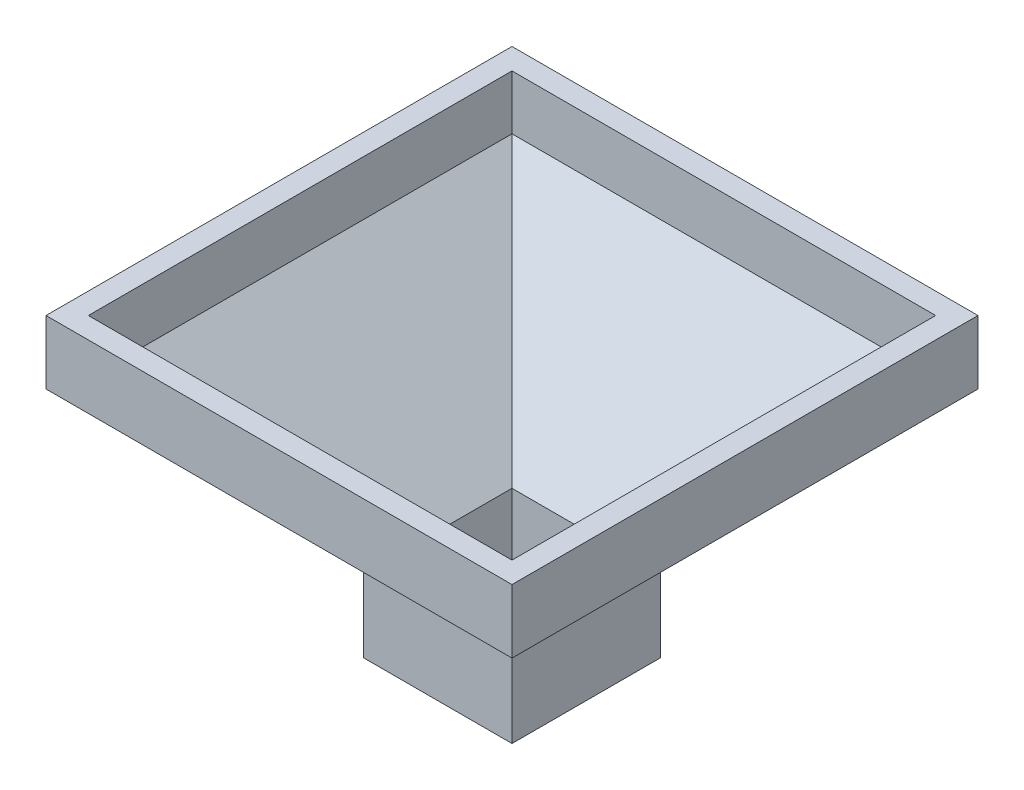
SolidWorks part; units mm, degrees
ref_plane "Alzado" through (0, 0, 0) normal (0, 0, 1) x (1, 0, 0)
ref_plane "Planta" through (0, 0, 0) normal (0, 1, 0) x (1, 0, 0)
ref_plane "Vista lateral" through (0, 0, 0) normal (1, 0, 0) x (0, 0, -1)
sketch "Croquis1" plane through (0, 0, 0) normal (0, 1, 0) x (1, 0, 0)
  line L1 (-110, -110) -> (110, -110)
  line L2 (-110, -110) -> (-110, 110)
  line L3 (-110, 110) -> (110, 110)
  line L4 (110, -110) -> (110, 110)
  line L5 (-110, -110) -> (110, 110) construction
  line L6 (-110, 110) -> (110, -110) construction
  point P0 (0, 0)
  dimension "D1" = 220
  dimension "D2" = 220
extrude "Saliente-Extruir1" add sketch "Croquis1" against normal blind 100
sketch "Croquis2" plane through (0, -100, 0) normal (0, -1, 0) x (1, 0, 0)
  line L1 (-35, -35) -> (35, -35)
  line L2 (-35, -35) -> (-35, 35)
  line L3 (-35, 35) -> (35, 35)
  line L4 (35, -35) -> (35, 35)
  line L5 (-35, -35) -> (35, 35) construction
  line L6 (-35, 35) -> (35, -35) construction
  point P0 (0, 0)
  dimension "D1" = 70
  dimension "D2" = 70
extrude "Cortar-Extruir1" cut sketch "Croquis2" against normal blind 70 draft 47 flip side to cut
sketch "Croquis3" plane through (0, -100, 0) normal (0, -1, 0) x (1, 0, 0)
  line L1 (-25, -25) -> (25, -25)
  line L2 (-25, -25) -> (-25, 25)
  line L3 (-25, 25) -> (25, 25)
  line L4 (25, -25) -> (25, 25)
  line L5 (-25, -25) -> (25, 25) construction
  line L6 (-25, 25) -> (25, -25) construction
  line L7 (35, -35) -> (-35, -35)
  line L8 (35, -35) -> (35, 35)
  line L9 (35, 35) -> (-35, 35)
  line L10 (-35, -35) -> (-35, 35)
  line L11 (35, -35) -> (-35, 35) construction
  line L12 (35, 35) -> (-35, -35) construction
  point P0 (0, 0)
  point P6 (0, 0)
  line M4 (-35, -35) -> (35, -35)
  line M5 (35, -35) -> (35, 35)
  line M6 (35, 35) -> (-35, 35)
  line M7 (-35, 35) -> (-35, -35)
  dimension "D1" = 50
  dimension "D2" = 50
  dimension "D3" = 70
  dimension "D4" = 70
extrude "Saliente-Extruir2" add sketch "Croquis3" along normal blind 40 contours L4 L1 L2 L3 M7 M4 M5 M6 | L2 L1 L4 L3 region at (0, -100, -34.0101)
shell "Vaciado1" thickness 10 removed face at (0, 0, 0)
extrude "Cortar-Extruir2" cut sketch "Croquis3<3>" along normal blind 40 contours L1 L4 L3 L2 region at (0, -100, 0)
sketch "Croquis3<3>" plane through (0, -100, 0) normal (0, -1, 0) x (1, 0, 0) same geometry as "Croquis3"
sketch "Croquis5" plane through (0, 0, 0) normal (0, 1, 0) x (1, 0, 0)
  line L0 (0, 0) -> (-141.4214, -141.4214)
  line L1 (0, 0) -> (141.4214, -141.4214)
  line L2 (-200, 0) -> (200, 0) construction
  arc A0 (141.4214, -141.4214) -> (-141.4214, -141.4214) centre (0, 0) ccw
  dimension "D1" = 400
  dimension "D2" = 45
